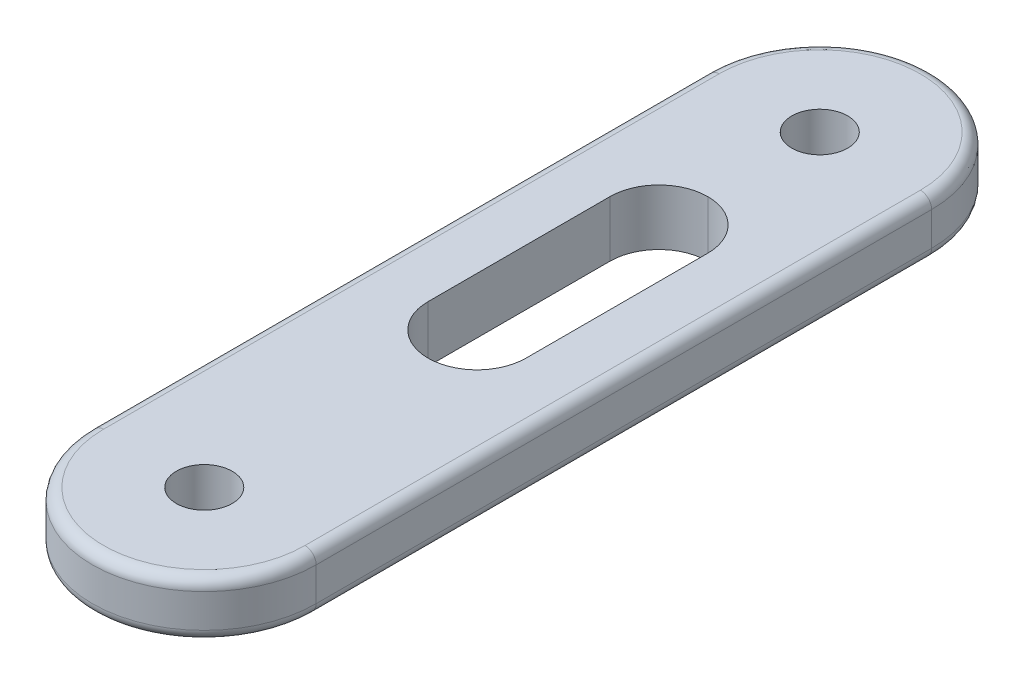
SolidWorks part; units mm, degrees
material "Cast Alloy Steel"
ref_plane "Front Plane" through (0, 0, 0) normal (0, 0, 1) x (1, 0, 0)
ref_plane "Top Plane" through (0, 0, 0) normal (0, 1, 0) x (1, 0, 0)
ref_plane "Right Plane" through (0, 0, 0) normal (1, 0, 0) x (0, 0, -1)
sketch "Sketch1" plane through (0, 0, 0) normal (0, 1, 0) x (1, 0, 0)
  line L0 (12.7, 95.25) -> (12.7, 0) construction
  line L1 (0, 0) -> (25.4, 0)
  line L2 (0, 0) -> (0, 95.25)
  line L3 (0, 95.25) -> (25.4, 95.25)
  line L4 (25.4, 0) -> (25.4, 95.25)
  line L5 (7.1437, 69.85) -> (18.2562, 69.85)
  line L6 (7.1437, 69.85) -> (7.1437, 38.1)
  line L7 (7.1437, 38.1) -> (18.2562, 38.1)
  line L8 (18.2562, 69.85) -> (18.2562, 38.1)
  circle A0 centre (12.7, 82.55) radius 3.175
  circle A1 centre (12.7, 12.7) radius 3.175
  point P11 (12.7, 69.85)
  dimension "D1" = 6.35
  dimension "D2" = 12.7
  dimension "D3" = 25.4
  dimension "D4" = 12.7
  dimension "D5" = 12.7
  dimension "D6" = 25.4
  dimension "D7" = 31.75
  dimension "D8" = 11.1125
extrude "Boss-Extrude1" add sketch "Sketch1" along normal blind 6.35
sketch "Sketch2" plane through (0, 6.35, 0) normal (0, 1, 0) x (1, 0, 0)
  line L0 (0, 0) -> (25.4, 0) construction
  line L1 (25.4, 95.25) -> (0, 95.25) construction
  circle A0 centre (12.7, 82.55) radius 12.7
  circle A1 centre (12.7, 12.7) radius 12.7
  line M3 (25.4, 95.25) -> (0, 95.25)
  line M5 (0, 0) -> (25.4, 0)
  line M13 (0, 95.25) -> (0, 0)
  line M14 (25.4, 0) -> (25.4, 95.25)
extrude "Cut-Extrude1" cut sketch "Sketch2" against normal through all contours A0 M3 M13 | A0 M14 M3 | A1 M13 M5 | A1 M5 M14 region at (22.5632, 6.35, -92.4132) region at (2.8368, 6.35, -92.4132) region at (22.5632, 6.35, -2.8368) region at (2.8368, 6.35, -2.8368)
fillet "Fillet1" radius 1.27 8 edges at (0, 6.35, -47.625) (0, 0, -47.625) (25.4, 0, -47.625) (25.4, 6.35, -47.625) (12.7, 0, 0) (12.7, 0, -95.25) (12.7, 6.35, 0) (12.7, 6.35, -95.25)
fillet "Fillet2" radius 5.5562 4 edges at (7.1437, 3.175, -38.1) (18.2562, 3.175, -38.1) (18.2562, 3.175, -69.85) (7.1437, 3.175, -69.85)
